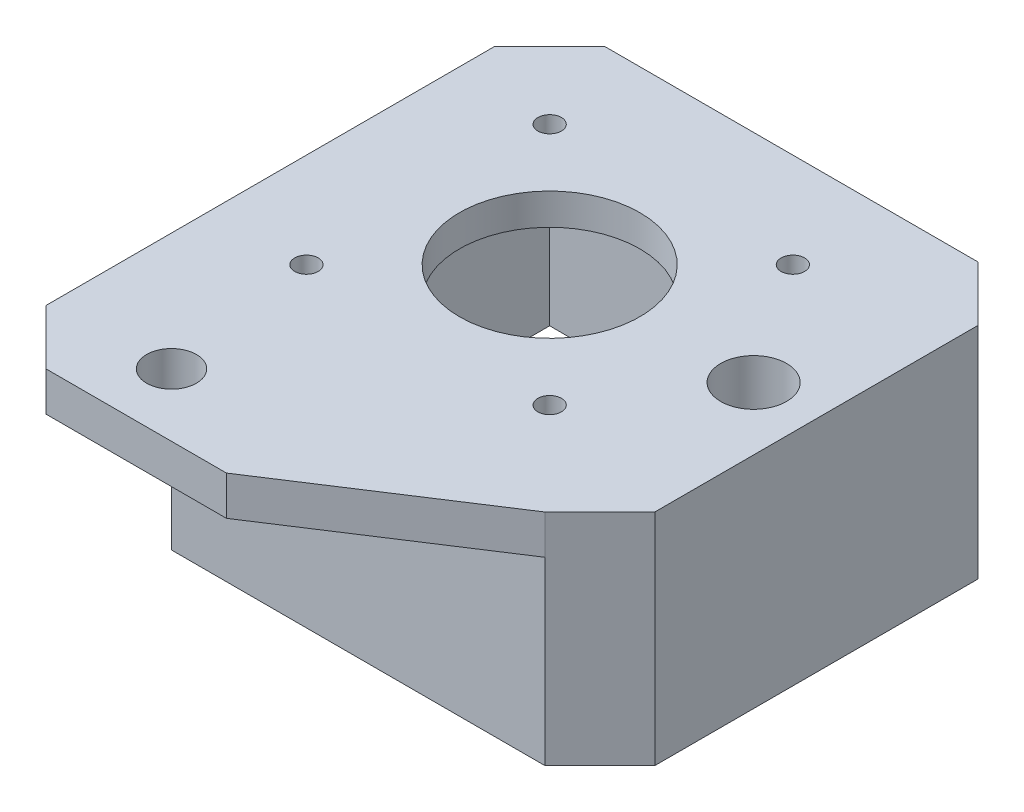
SolidWorks part; units mm, degrees
ref_plane "Front Plane" through (0, 0, 0) normal (0, 0, 1) x (1, 0, 0)
ref_plane "Top Plane" through (0, 0, 0) normal (0, 1, 0) x (1, 0, 0)
ref_plane "Right Plane" through (0, 0, 0) normal (1, 0, 0) x (0, 0, -1)
sketch "Sketch1" plane through (0, 0, 0) normal (0, 1, 0) x (1, 0, 0)
  line L0 (0, 21) -> (55, 21) construction
  line L1 (0, 0) -> (55, 0)
  line L2 (0, 0) -> (0, 42)
  line L3 (0, 42) -> (55, 42)
  line L4 (55, 0) -> (55, 42)
  line L5 (21, 42) -> (21, 0) construction
  circle A0 centre (47, 21) radius 4.2
  circle A1 centre (21, 21) radius 11.5
  circle A2 centre (5.5, 36.5) radius 1.5
  circle A3 centre (36.5, 36.5) radius 1.5
  circle A4 centre (5.5, 5.5) radius 1.5
  circle A5 centre (36.5, 5.5) radius 1.5
  point P8 (55, 21)
  dimension "D2" = 23
  dimension "D4" = 8.4
  dimension "D9" = 3
  dimension "D1" = 26
  dimension "D3" = 42
  dimension "D5" = 21
  dimension "D6" = 55
  dimension "D7" = 15.5
  dimension "D8" = 15.5
extrude "Boss-Extrude1" add sketch "Sketch1" along normal blind 4
sketch "Sketch2" plane through (0, 0, 0) normal (0, -1, 0) x (1, 0, 0)
  line L0 (0, 0) -> (55, 0) construction
  line L1 (40.4, 0) -> (42.25, 0)
  line L2 (40.4, 0) -> (40.4, -42)
  line L3 (40.4, -42) -> (42.25, -42)
  line L4 (42.25, 0) -> (42.25, -42)
  line L5 (55, -42) -> (0, -42) construction
  line L6 (55, 0) -> (55, -42) construction
  line L7 (55, -11) -> (42.25, -11)
  line L8 (55, -11) -> (55, -31)
  line L9 (55, -31) -> (42.25, -31)
  line L10 (42.25, -11) -> (42.25, -31)
  circle A0 centre (47, -21) radius 6.6
  circle A1 centre (47, -21) radius 4.2
  circle A2 centre (47, -21) radius 4.2 construction
  point P25 (55, -21)
  point P26 (55, -21)
  circle M7 centre (47, -21) radius 4.2
  line M10 (55, -42) -> (55, 0)
  dimension "D1" = 2.4
  dimension "D2" = 1.85
  dimension "D3" = 20
extrude "Boss-Extrude2" add sketch "Sketch2" along normal blind 20 contours L4 A0 L10 M7 | A0 L10 L9 L7 L4 M10 region at (48.625, 0, -11.2372) region at (49.4057, 0, -15.0414)
sketch "Sketch3" plane through (0, -20, 0) normal (0, -1, 0) x (1, 0, 0)
  line L1 (55, -31) -> (42.25, -31)
  line L2 (55, -31) -> (55, -11)
  line L3 (55, -11) -> (42.25, -11)
  line L4 (42.25, -31) -> (42.25, -11)
extrude "Boss-Extrude3" add sketch "Sketch3" along normal blind 4
sketch "Sketch4" plane through (0, 0, 0) normal (0, -1, 0) x (1, 0, 0)
  line L0 (42.25, -11) -> (42.25, -31) construction
  line L1 (42.25, 0.25) -> (-0.25, 0.25)
  line L2 (42.25, 0.25) -> (42.25, -42.25)
  line L3 (42.25, -42.25) -> (-0.25, -42.25)
  line L4 (-0.25, 0.25) -> (-0.25, -42.25)
  line L9 (48.6, 6.6) -> (-6.6, 6.6)
  line L10 (48.6, 6.6) -> (48.6, -48.6)
  line L11 (48.6, -48.6) -> (-6.6, -48.6)
  line L12 (-6.6, 6.6) -> (-6.6, -48.6)
  line L13 (55, -42) -> (0, -42) construction
  line L14 (0, -42) -> (0, 0) construction
  line L15 (0, 0) -> (55, 0) construction
  dimension "D1" = 0.25
  dimension "D2" = 0.25
  dimension "D3" = 0.25
  dimension "D4" = 6.35
  dimension "D5" = 6.35
  dimension "D6" = 6.35
  dimension "D7" = 6.35
extrude "Boss-Extrude4" add sketch "Sketch4" along normal up to surface (24 mm away) contours L10 L9 L12 L11 | L2 L1 L4 L3 up to face at (48.625, -24, -21)
sketch "Sketch5" plane through (0, 0, 0) normal (0, 1, 0) x (1, 0, 0)
  circle A0 centre (47, 21) radius 4.2
  circle A1 centre (47, 21) radius 4.2 construction
extrude "Cut-Extrude1" cut sketch "Sketch5" against normal up to surface (20 mm away) up to face at (49.9, -20, -21)
sketch "Sketch6" plane through (48.6, 0, 0) normal (1, 0, 0) x (0, 0, -1)
  line L0 (0, 4) -> (42, 4) construction
  line L1 (-6.6, 0) -> (0, 0)
  line L2 (-6.6, 0) -> (-6.6, 4)
  line L3 (-6.6, 4) -> (0, 4)
  line L4 (0, 0) -> (0, 4)
  line L5 (0, 4) -> (42, 4)
  line L6 (21, 4) -> (21, -2.4275) construction
  line L7 (48.6, 4) -> (42, 4)
  line L8 (42, 0) -> (42, 4)
  line L9 (48.6, 0) -> (42, 0)
  line L10 (48.6, 0) -> (48.6, 4)
  point P9 (21, 4)
  line M3 (0, 0) -> (-6.6, 0)
extrude "Boss-Extrude6" add sketch "Sketch6" against normal up to surface (48.6 mm away) contours L9 L10 L7 L8 | L4 L3 L2 M3 region at (48.6, 2, 3.3) region at (48.6, 2, -45.3) up to face at (0, 2, -21)
sketch "Sketch7" plane through (0, 0, -48.6) normal (0, 0, -1) x (-1, 0, 0)
  line L0 (6.6, -24) -> (6.6, 0) construction
  line L1 (0, 0) -> (6.6, 0)
  line L2 (0, 0) -> (0, 4)
  line L3 (0, 4) -> (6.6, 4)
  line L4 (6.6, 0) -> (6.6, 4)
extrude "Boss-Extrude7" add sketch "Sketch7" against normal up to surface (55.2 mm away) up to face at (14, -6.6667, 6.6)
sketch "Sketch8" plane through (48.6, 0, 0) normal (1, 0, 0) x (0, 0, -1)
  line L6 (42, 0) -> (31, 0)
  line L7 (31, 0) -> (31, -24)
  line L8 (31, -24) -> (48.6, -24)
  line L9 (48.6, -24) -> (48.6, 4)
  line L10 (48.6, 4) -> (42, 4)
  line L11 (42, 4) -> (42, 0)
  line L12 (42, 0) -> (31, 0)
  line L13 (31, 0) -> (31, -24)
  line L14 (31, -24) -> (48.6, -24)
  line L15 (48.6, -24) -> (48.6, 4)
  line L16 (48.6, 4) -> (42, 4)
  line L17 (42, 4) -> (42, 0)
  line L18 (11, -24) -> (11, 0)
  line L19 (11, 0) -> (0, 0)
  line L20 (0, 0) -> (0, 4)
  line L21 (0, 4) -> (-6.6, 4)
  line L22 (-6.6, 4) -> (-6.6, -24)
  line L23 (-6.6, -24) -> (11, -24)
  line L24 (11, -24) -> (11, 0)
  line L25 (11, 0) -> (0, 0)
  line L26 (0, 0) -> (0, 4)
  line L27 (0, 4) -> (-6.6, 4)
  line L28 (-6.6, 4) -> (-6.6, -24)
  line L29 (-6.6, -24) -> (11, -24)
  dimension "D1" = 0
  dimension "D2" = 0
extrude "Boss-Extrude8" add sketch "Sketch8" along normal up to surface (6.4 mm away) up to face at (55, -5, -21)
sketch "Sketch9" plane through (0, 4, 0) normal (0, 1, 0) x (1, 0, 0)
  line L0 (55, 0.4) -> (48, -6.6)
  line L1 (55, -6.6) -> (55, 48.6) construction
  line L2 (-6.6, -6.6) -> (55, -6.6) construction
  line L3 (48, -6.6) -> (55, -6.6)
  line L4 (55, -6.6) -> (55, 0.4)
  line L5 (55, 41.6) -> (48, 48.6)
  line L6 (-6.6, 48.6) -> (55, 48.6) construction
  line L7 (48, 48.6) -> (55, 48.6)
  line L8 (55, 48.6) -> (55, 41.6)
  line L9 (0.4, 48.6) -> (-6.6, 48.6)
  line L10 (-6.6, 48.6) -> (-6.6, 41.6)
  line L11 (-6.6, -6.6) -> (-6.6, 48.6) construction
  line L12 (-6.6, 41.6) -> (0.4, 48.6)
  line L13 (0.4, -6.6) -> (-6.6, 0.4)
  line L14 (-6.6, 0.4) -> (-6.6, -6.6)
  line L15 (-6.6, -6.6) -> (0.4, -6.6)
  dimension "D1" = 7
extrude "Cut-Extrude2" cut sketch "Sketch9" against normal up to surface (28 mm away) up to face at (24.2, -24, -21)
sketch "Sketch10" plane through (0, 4, 0) normal (0, 1, 0) x (1, 0, 0)
  line L0 (-6.6, 0.4) -> (-6.6, 41.6) construction
  line L1 (-6.6, 0.4) -> (23.4, 0.4)
  line L2 (-6.6, 0.4) -> (-6.6, -22.6)
  line L3 (-6.6, -22.6) -> (23.4, -22.6)
  line L4 (23.4, 0.4) -> (23.4, -22.6)
  line L5 (0.4, -6.6) -> (-6.6, 0.4) construction
  line L6 (23.4, -22.6) -> (48, -6.6)
  line L7 (48, -6.6) -> (23.4, -6.6)
  line L8 (0.4, -6.6) -> (48, -6.6) construction
  line L9 (23.4, -6.6) -> (23.4, -22.6)
  line L10 (-6.6, -15.6) -> (0.4, -22.6)
  circle A0 centre (8.4, -14.6) radius 3.175
  point P7 (1.3897, -22.6)
  line M10 (-6.6, 0.4) -> (0.4, -6.6)
  line M11 (0.4, -6.6) -> (48, -6.6)
  dimension "D3" = 6.35
  dimension "D1" = 15
  dimension "D2" = 15
  dimension "D4" = 15
  dimension "D5" = 8
  dimension "D6" = 7
  dimension "D7" = 7
extrude "Boss-Extrude10" add sketch "Sketch10" against normal blind 5 contours L2 L10 L3 L4 A0 M11 M10 | L4 L6 M11 region at (-3.3673, 4, 3.3673) region at (31.6, 4, 11.9333)
equation "\"8mm hole\" = 8.4mm"
equation "\"22mm hole\"= 23mm"
equation "\"D2@Sketch1\"=\"22mm hole\""
equation "\"D4@Sketch1\"=\"8mm hole\""
